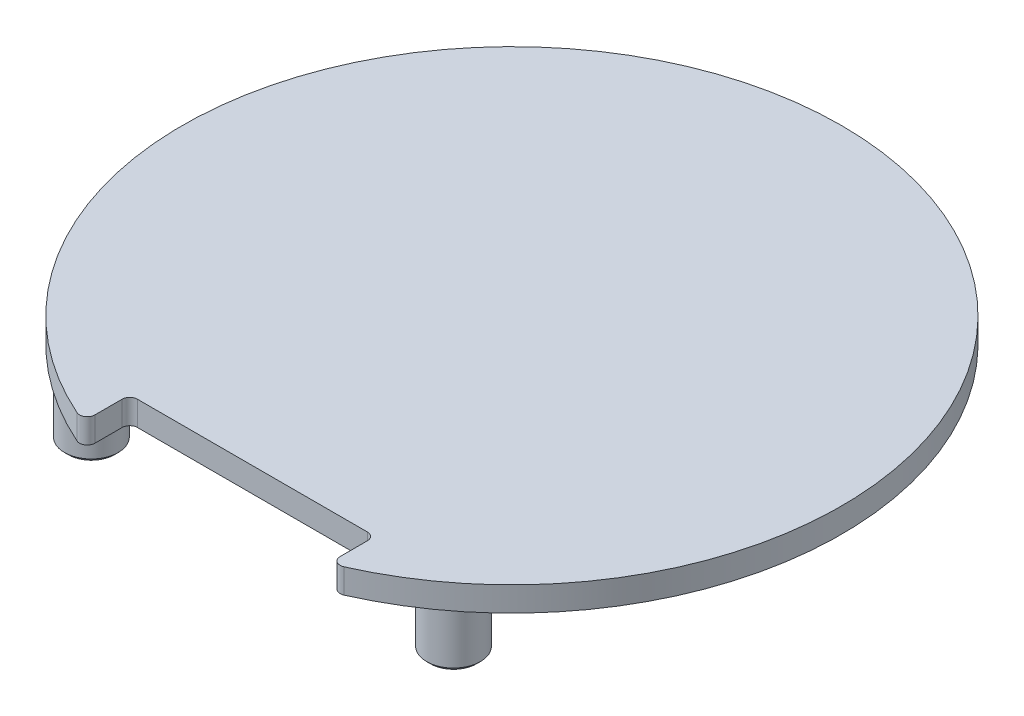
SolidWorks part; units mm, degrees
ref_plane "Ebene vorne" through (0, 0, 0) normal (0, 0, 1) x (1, 0, 0)
ref_plane "Ebene oben" through (0, 0, 0) normal (0, 1, 0) x (1, 0, 0)
ref_plane "Ebene rechts" through (0, 0, 0) normal (1, 0, 0) x (0, 0, -1)
sketch "Skizze1" plane through (0, 0, 0) normal (0, 1, 0) x (1, 0, 0)
  line L0 (7.5, -16.9281) -> (-7.5, -16.9281)
  line L7 (8, -17.4281) -> (8, -19.2029)
  line L10 (-8, -17.4281) -> (-8, -19.2029)
  arc A0 (8.7024, -19.6601) -> (-8.7024, -19.6601) centre (0, 0) ccw
  arc A1 (-7.5, -16.9281) -> (-8, -17.4281) centre (-7.5, -17.4281) ccw
  arc A2 (-8, -19.2029) -> (-8.7024, -19.6601) centre (-8.5, -19.2029) cw
  arc A3 (8, -19.2029) -> (8.7024, -19.6601) centre (8.5, -19.2029) ccw
  arc A4 (7.5, -16.9281) -> (8, -17.4281) centre (7.5, -17.4281) cw
  dimension "D1" = 0.5
extrude "Aufsatz-Linear austragen1" add sketch "Skizze1" along normal blind 1.6
sketch "Skizze2" plane through (0, 0, 0) normal (0, 1, 0) x (1, 0, 0)
  circle A0 centre (0, 19.431) radius 1.75
  circle A1 centre (-11.811, -15.621) radius 1.75
  circle A2 centre (11.811, -15.621) radius 1.75
  circle A3 centre (0, 19.431) radius 0.8
  circle A4 centre (-11.811, -15.621) radius 0.8
  circle A5 centre (11.811, -15.621) radius 0.8
  dimension "D1" = 19.431
  dimension "D2" = 11.811
  dimension "D4" = 11.811
  dimension "D3" = 15.621
extrude "Aufsatz-Linear austragen2" add sketch "Skizze2" against normal blind 3.6 separate body
extrude "Aufsatz-Linear austragen3" add sketch "Skizze2<2>" against normal blind 0.5 contours A0 A3 | A4 | A1 A4 | A2 A5 | A3 | A5 region at (-1.7005, 0, -19.431) region at (-13.5115, 0, 15.621) region at (10.1105, 0, 15.621) region at (-11.811, 0, 15.621)
sketch "Skizze2<2>" plane through (0, 0, 0) normal (0, 1, 0) x (1, 0, 0) same geometry as "Skizze2"
thread "Gewinde1" pitch 0.4 method cut profile "Gewindeprofil1" start angle 0, offset 1, length 0, pitch 0.4, diameter 1.6
ref_plane "Ebene1" through (12.611, -4.6, 15.621) normal (0, 0, 1) x (1, 0, 0)
sketch "Gewindeprofil1" plane through (12.611, -4.6, 15.621) normal (0, 0, 1) x (1, 0, 0)
  line L0 (0, 0) -> (0, 0.4) construction
  line L1 (0, 0) -> (0.2165, 0.125)
  line L2 (0.2165, 0.125) -> (0.2165, 0.175)
  line L3 (0.2165, 0.175) -> (0, 0.3)
  line L4 (0.2165, 0.15) -> (0, 0.15) construction
  line L11 (0, 0) -> (0, 0.3)
  point P2 (0, 0)
  dimension "Pitch" = 0.4
  dimension "Profile_Angle" = 60
  dimension "Profile_Land" = 0.05
  dimension "Profile_Height" = 0.2165
thread "Gewinde2" pitch 0.4 method cut profile "Gewindeprofil2" start angle 0, offset 1, length 0, pitch 0.4, diameter 1.6
ref_plane "Ebene2" through (0.8, -4.6, -19.431) normal (0, 0, 1) x (1, 0, 0)
sketch "Gewindeprofil2" plane through (0.8, -4.6, -19.431) normal (0, 0, 1) x (1, 0, 0)
  line L0 (0, 0) -> (0, 0.4) construction
  line L1 (0, 0) -> (0.2165, 0.125)
  line L2 (0.2165, 0.125) -> (0.2165, 0.175)
  line L3 (0.2165, 0.175) -> (0, 0.3)
  line L4 (0.2165, 0.15) -> (0, 0.15) construction
  line L11 (0, 0) -> (0, 0.3)
  point P2 (0, 0)
  dimension "Pitch" = 0.4
  dimension "Profile_Angle" = 60
  dimension "Profile_Land" = 0.05
  dimension "Profile_Height" = 0.2165
thread "Gewinde3" pitch 0.4 method cut profile "Gewindeprofil3" start angle 0, offset 1, length 0, pitch 0.4, diameter 1.6
ref_plane "Ebene3" through (-11.011, -4.6, 15.621) normal (0, 0, 1) x (1, 0, 0)
sketch "Gewindeprofil3" plane through (-11.011, -4.6, 15.621) normal (0, 0, 1) x (1, 0, 0)
  line L0 (0, 0) -> (0, 0.4) construction
  line L1 (0, 0) -> (0.2165, 0.125)
  line L2 (0.2165, 0.125) -> (0.2165, 0.175)
  line L3 (0.2165, 0.175) -> (0, 0.3)
  line L4 (0.2165, 0.15) -> (0, 0.15) construction
  line L11 (0, 0) -> (0, 0.3)
  point P2 (0, 0)
  dimension "Pitch" = 0.4
  dimension "Profile_Angle" = 60
  dimension "Profile_Land" = 0.05
  dimension "Profile_Height" = 0.2165
chamfer "Fase1" distance 0.25 angle 45 3 edges at (0, -3.6, -17.681) (11.811, -3.6, 17.371) (-11.811, -3.6, 17.371)
